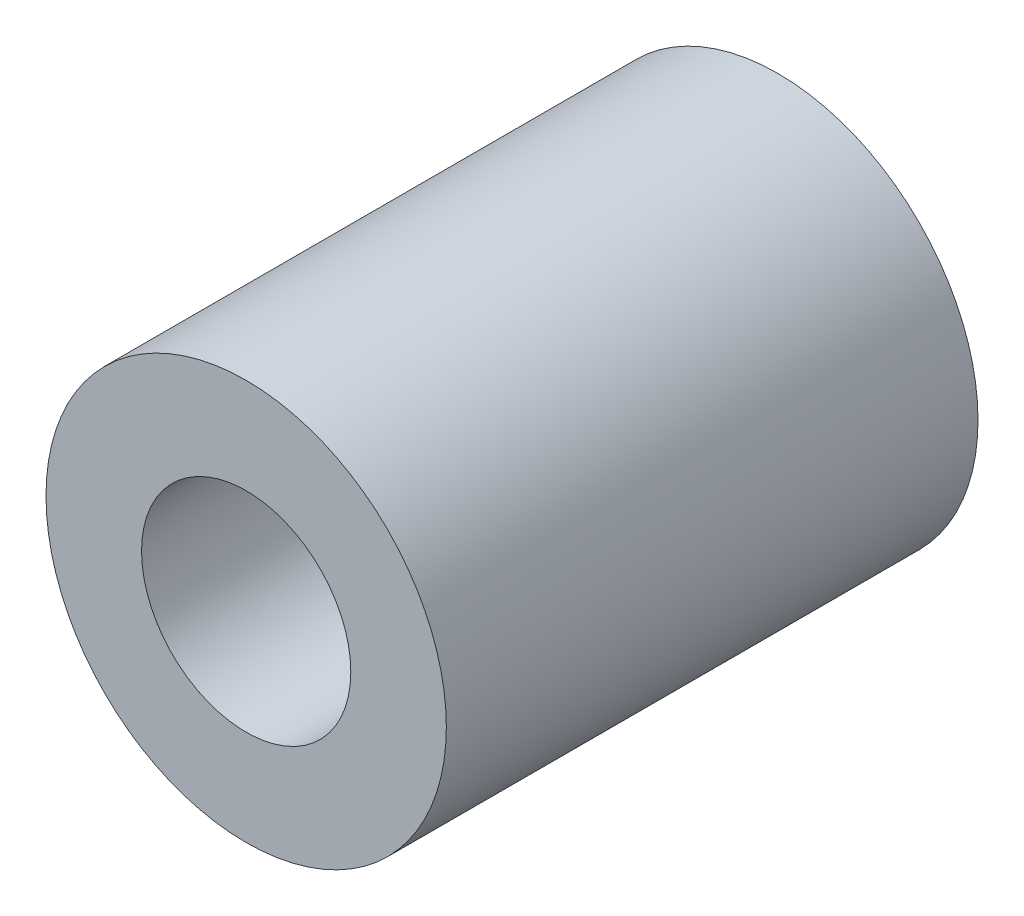
SolidWorks part; units mm, degrees
ref_plane "Front Plane" through (0, 0, 0) normal (0, 0, 1) x (1, 0, 0)
ref_plane "Top Plane" through (0, 0, 0) normal (0, 1, 0) x (1, 0, 0)
ref_plane "Right Plane" through (0, 0, 0) normal (1, 0, 0) x (0, 0, -1)
sketch "Sketch1" plane through (0, 0, 0) normal (0, 0, 1) x (1, 0, 0)
  circle A0 centre (0, 0) radius 2.4892
  circle A1 centre (0, 0) radius 4.7625
  dimension "D1" = 4.9784
  dimension "D2" = 9.525
extrude "Boss-Extrude1" add sketch "Sketch1" along normal mid plane 12.6492
